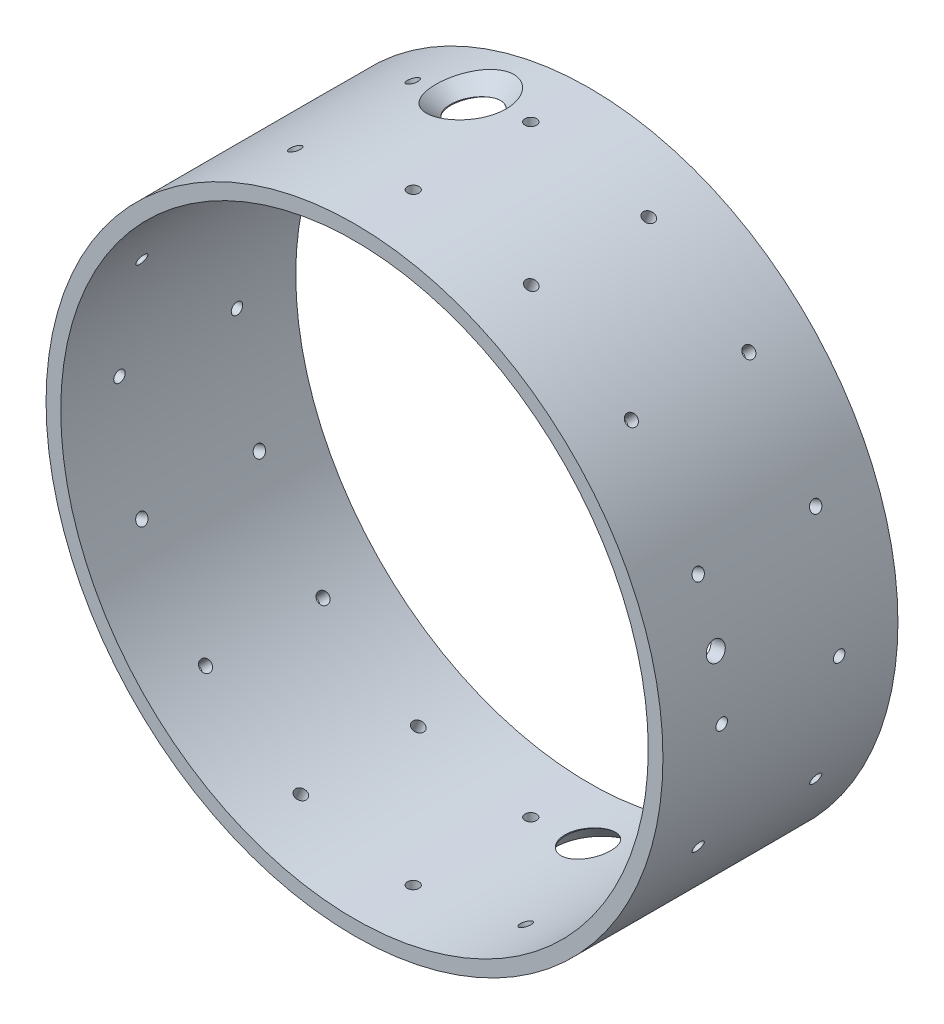
SolidWorks part; units mm, degrees
material "6061-T6 (SS)"
ref_plane "Front Plane" through (0, 0, 0) normal (0, 0, 1) x (1, 0, 0)
ref_plane "Top Plane" through (0, 0, 0) normal (0, 1, 0) x (1, 0, 0)
ref_plane "Right Plane" through (0, 0, 0) normal (1, 0, 0) x (0, 0, -1)
sketch "Sketch1" plane through (0, 0, 0) normal (0, 0, 1) x (1, 0, 0)
  circle A0 centre (0, 0) radius 63.5
  circle A1 centre (0, 0) radius 66.675
extrude "Extrude1" add sketch "Sketch1" along normal blind 50.8
ref_plane "Plane1" through (0, 0, 12.7) normal (0, 0, -1) x (-1, 0, 0)
sketch "Sketch2" plane through (0, 0, 12.7) normal (0, 0, -1) x (-1, 0, 0)
  line L0 (0, 0) -> (0, 66.675) construction
  line L1 (0, 0) -> (13.0076, 65.3939) construction
  line L2 (0, 0) -> (-65.3939, 13.0076) construction
  circle A0 centre (0, 0) radius 66.675 construction
  dimension "D1" = 11.25
  dimension "D2" = 90
ref_plane "Plane4" through (0, 66.675, 12.7) normal (0, 1, 0) x (-1, 0, 0)
sketch "Sketch7" plane through (0, 66.675, 12.7) normal (0, 1, 0) x (-1, 0, 0)
  line L0 (0, 0) -> (0, 25.4) construction
  dimension "D1" = 25.4
hole_wizard "#40 (0.098) Diameter Hole2" positions "Sketch9" profile "Sketch8" hole size "#40" standard "Ansi Inch"
sketch "Sketch9" plane through (0, 66.675, 12.7) normal (0, 1, 0) x (-1, 0, 0)
  point P1 (0, 0)
  point P4 (0, 25.4)
sketch "Sketch8" plane through (0, 66.675, 12.7) normal (1, 0, 0) x (0, 0, 1)
  line L0 (0, 0) -> (0, 13.4478)
  line L1 (0, 13.4478) -> (1.2446, 12.7)
  line L2 (1.2446, 12.7) -> (1.2446, 0)
  line L5 (1.2446, 0) -> (0, 0)
  line L10 (0, 13.4478) -> (-1.2446, 12.7) construction
  line L11 (0, -6.35) -> (0, 107.95) construction
  dimension "Hole Dia." = 2.4892
  dimension "Hole Depth" = 12.7
  dimension "Drill Angle" = 118
pattern_circular "CirPattern1" count 16 over 360 about axis through (0, 0, 50.8) along (0, 0, -1) of "#40 (0.098) Diameter Hole2"
ref_plane "Plane5" through (-13.0076, 65.3939, 12.7) normal (-0.1951, 0.9808, 0) x (-0.9808, -0.1951, 0)
hole_wizard "3/8 Clearance Hole1" positions "Sketch13" profile "Sketch14" hole size "3/8" standard "Ansi Inch"
sketch "Sketch13" plane through (-13.0076, 65.3939, 12.7) normal (-0.1951, 0.9808, 0) x (-0.9808, -0.1951, 0)
  point P1 (0, 0)
sketch "Sketch14" plane through (-13.0076, 65.3939, 12.7) normal (0, 0, 1) x (-0.9808, -0.1951, 0)
  line L0 (0, 0) -> (0, 15.9835)
  line L1 (0, 15.9835) -> (5.0419, 12.954)
  line L2 (5.0419, 12.954) -> (5.0419, 3.175)
  line L3 (5.0419, 3.175) -> (8.2169, 0)
  line L5 (8.2169, 0) -> (0, 0)
  line L6 (-5.0419, 3.175) -> (-8.2169, 0) construction
  line L10 (0, 15.9835) -> (-5.0419, 12.954) construction
  line L11 (0, -6.35) -> (0, 107.95) construction
  dimension "Hole Dia." = 10.0838
  dimension "Hole Depth" = 12.954
  dimension "Near C'Sink Dia." = 16.4338
  dimension "Near C'Sink Angle" = 90
  dimension "Drill Angle" = 118
ref_plane "Plane6" through (0, 0, 12.7) normal (-0.1951, 0.9808, 0) x (-0.9808, -0.1951, 0)
mirror "Mirror1" about plane through (0, 0, 12.7) normal (-0.1951, 0.9808, 0) of "3/8 Clearance Hole1"
ref_plane "Plane7" through (65.3939, 13.0076, 12.7) normal (0.9808, 0.1951, 0) x (0, 0, -1)
sketch "Sketch17" plane through (65.3939, 13.0076, 12.7) normal (0.9808, 0.1951, 0) x (0, 0, -1)
  line L0 (0, 0) -> (-25.4, 0) construction
  dimension "D1" = 25.4
hole_wizard "#10-32 Tapped Hole1" positions "Sketch16" profile "Sketch15" tap size "#10-32" standard "Ansi Inch"
sketch "Sketch16" plane through (65.3939, 13.0076, 12.7) normal (0.9808, 0.1951, 0) x (0, 0, -1)
  point P4 (-25.4, 0)
sketch "Sketch15" plane through (65.3939, 13.0076, 38.1) normal (0, 0, 1) x (-0.1951, 0.9808, 0)
  line L0 (0, 0) -> (0, 14.9293)
  line L1 (0, 14.9293) -> (2.0193, 13.716)
  line L2 (2.0193, 13.716) -> (2.0193, 0)
  line L5 (2.0193, 0) -> (0, 0)
  line L10 (0, 14.9293) -> (-2.0193, 13.716) construction
  line L11 (0, -6.35) -> (0, 107.95) construction
  dimension "Tap Drill Dia." = 4.0386
  dimension "Tap Drill Depth" = 13.716
  dimension "Drill Angle" = 118
cosmetic thread "Hole Thread1" parameters "D1"=3.2071, "D2"=4.826
